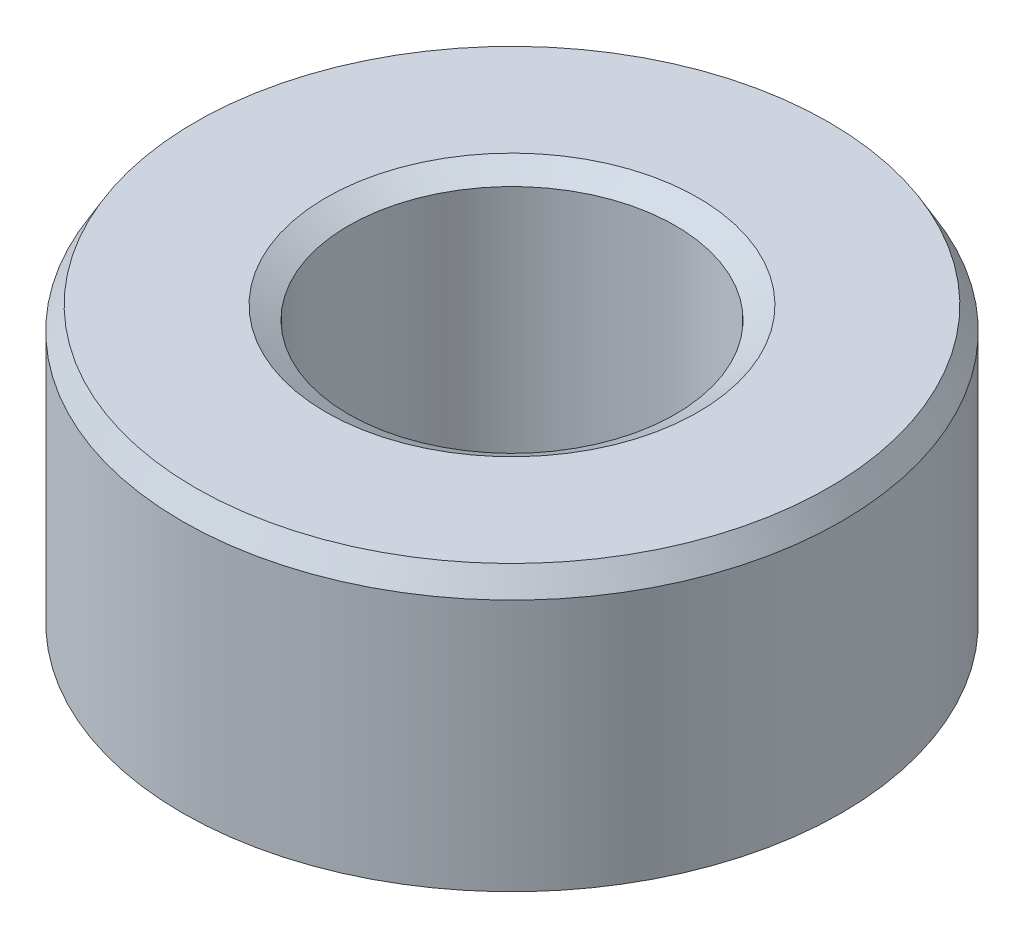
SolidWorks part; units mm, degrees
ref_plane "Front Plane" through (0, 0, 0) normal (0, 0, 1) x (1, 0, 0)
ref_plane "Top Plane" through (0, 0, 0) normal (0, 1, 0) x (1, 0, 0)
ref_plane "Right Plane" through (0, 0, 0) normal (1, 0, 0) x (0, 0, -1)
sketch "Sketch1" plane through (0, 0, 0) normal (0, 1, 0) x (1, 0, 0)
  circle A0 centre (0, 0) radius 55
  dimension "SLEEVE_OD" = 110
extrude "Boss-Extrude1" add sketch "Sketch1" along normal blind 48.0602
sketch "Sketch2" plane through (0, 0, 0) normal (0, 1, 0) x (1, 0, 0)
  circle A0 centre (0, 0) radius 27.2591
  dimension "BORE_D" = 54.5181
extrude "Cut-Extrude1" cut sketch "Sketch2" along normal through all
chamfer "Chamfer1" distance 3.761 angle 30 4 edges at (0, 48.0602, 27.2591) (0, 0, 27.2591) (0, 0, 55) (0, 48.0602, 55) first distance on face at (0, 48.0602, 27.2591) first distance on face at (0, 0, 27.2591) first distance on face at (0, 48.0602, 55)
